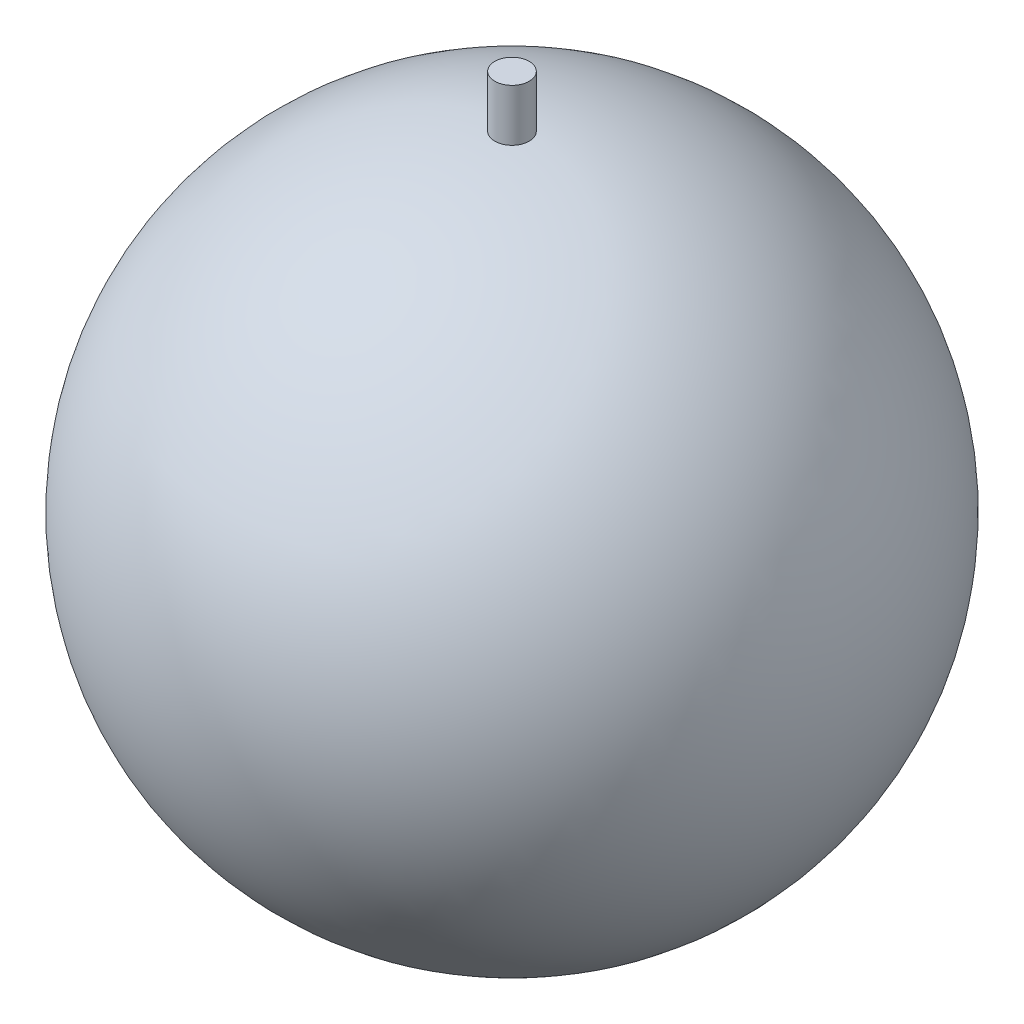
SolidWorks part; units mm, degrees
ref_plane "前视" through (0, 0, 0) normal (0, 0, 1) x (1, 0, 0)
ref_plane "上视" through (0, 0, 0) normal (0, 1, 0) x (1, 0, 0)
ref_plane "右视" through (0, 0, 0) normal (1, 0, 0) x (0, 0, -1)
sketch "Sketch2" plane through (0, 0, 0) normal (0, 0, 1) x (1, 0, 0)
  line L0 (14.5207, 55.1561) -> (14.5207, -8.325)
  arc A1 (14.5207, 55.1561) -> (14.5207, -8.325) centre (14.5207, 23.4156) ccw
ref_axis "Axis2" through (14.5207, 23.4156, 0) along (0, 1, 0)
revolve "Revolve6" add sketch "Sketch2" angle 360 about L0
ref_plane "Plane1" through (0, 55.1561, 0) normal (0, 1, 0) x (1, 0, 0)
sketch "Sketch3" plane through (0, 55.1561, 0) normal (0, 1, 0) x (1, 0, 0)
  circle A0 centre (14.5207, 0) radius 1.6573
extrude "Boss-Extrude1" add sketch "Sketch3" along normal blind 5 separate body
